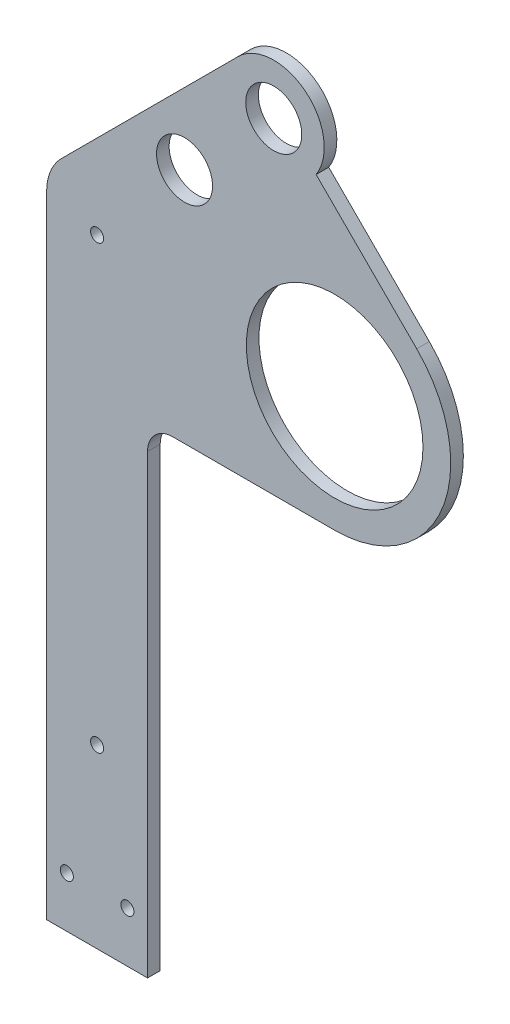
SolidWorks part; units mm, degrees
material "6061 合金"
ref_plane "前视基准面" through (0, 0, 0) normal (0, 0, 1) x (1, 0, 0)
ref_plane "上视基准面" through (0, 0, 0) normal (0, 1, 0) x (1, 0, 0)
ref_plane "右视基准面" through (0, 0, 0) normal (1, 0, 0) x (0, 0, -1)
other "Configuration Table"
sketch "草图1" plane through (0, 0, 0) normal (0, 0, 1) x (1, 0, 0)
  circle A0 centre (0, 0) radius 20
  circle A1 centre (0, 0) radius 11.1
  dimension "D1" = 40
  dimension "D2" = 22.2
extrude "凸台-拉伸1" add sketch "草图1" along normal blind 60 contours A1 | A0 region at (0, 0, 0)
ref_plane "基准面1" through (0, 0, 30) normal (0, 0, 1) x (1, 0, 0)
sketch "草图2" plane through (0, 0, 30) normal (0, 0, 1) x (1, 0, 0)
  line L0 (0, 0) -> (-70, -70) construction
  line L1 (-70, -70) -> (-70, -320) construction
  line L2 (0, -57.3148) -> (0, 49.9409) construction
  line L3 (-56.8582, 0) -> (46.4003, 0) construction
  line L4 (-14.1421, 14.1421) -> (-90, -61.7157)
  line L5 (14.1421, -14.1421) -> (-50, -78.2843)
  line L6 (-90, -61.7157) -> (-90, -320)
  line L7 (-50, -78.2843) -> (-50, -320)
  line L8 (-90, -320) -> (-50, -320)
  circle A2 centre (0, 0) radius 20 construction
  arc A3 (-14.1421, 14.1421) -> (14.1421, -14.1421) centre (0, 0) ccw
  dimension "D1" = 45
  dimension "D2" = 250
  dimension "D3" = 70
  dimension "D4" = 40
  dimension "D5" = 40
extrude "凸台-拉伸2" add sketch "草图2" along normal mid plane 60 contours L7 L8 L6 L4 A3 L5
sketch "草图4" plane through (0, 0, 60) normal (0, 0, 1) x (1, 0, 0)
  line L0 (-90, -61.7157) -> (-90, -320) construction
  line L1 (-90, -290) -> (-50, -290)
  line L2 (-90, -290) -> (-90, -350)
  line L4 (-50, -290) -> (-50, -350)
  line L5 (-50, -78.2843) -> (-50, -320) construction
  line L6 (-90, -320) -> (-50, -320) construction
  arc A0 (-90, -350) -> (-50, -350) centre (-70, -350) ccw
  circle A1 centre (-70, -350) radius 11
  dimension "D3" = 22
  dimension "D1" = 30
  dimension "D2" = 30
extrude "凸台-拉伸3" add sketch "草图4" along normal blind 5
mirror "镜向1" about plane through (0, 0, 30) normal (0, 0, 1) of "凸台-拉伸3"
sketch "草图5" plane through (0, 0, 0) normal (0, 1, 0) x (1, 0, 0)
  line L0 (0, 0) -> (0, -78.0582) construction
ref_plane "基准面2" through (-70, 0, 0) normal (-1, 0, 0) x (0, 0, 1)
sketch "草图7" plane through (-70, 0, 0) normal (-1, 0, 0) x (0, 0, 1)
  line L0 (-34.1239, -350) -> (109.535, -350) construction
sketch "草图8" plane through (0, 0, 60) normal (0, 0, 1) x (1, 0, 0)
  line L0 (0, 0) -> (-70, -70) construction
  circle A0 centre (-35.3553, -35.3553) radius 11.1
  dimension "D1" = 22.2
  dimension "D2" = 50
extrude "切除-拉伸1" cut sketch "草图8" against normal blind 100
fillet "圆角4" radius 20 2 edges at (-90, -61.7157, 30) (-50, -78.2843, 30)
fillet "圆角1" [suppressed] radius 50
fillet "圆角2" [suppressed] radius 3
sketch "草图9" plane through (0, 0, 65) normal (0, 0, 1) x (1, 0, 0)
  circle A0 centre (-70, -350) radius 13
  dimension "D1" = 26
extrude "切除-拉伸2" [suppressed] cut sketch "草图9" against normal blind 0.75
sketch "草图10" plane through (0, 0, -5) normal (0, 0, -1) x (-1, 0, 0)
  circle A0 centre (70, -350) radius 13
  dimension "D1" = 26
extrude "切除-拉伸3" [suppressed] cut sketch "草图10" against normal blind 0.75 contours A0
sketch "草图11" plane through (-90, 0, 0) normal (-1, 0, 0) x (0, 0, 1)
  circle A0 centre (48.5, -118.9949) radius 2.75
  circle A1 centre (48.5, -183.9949) radius 2.75
  circle A2 centre (48.5, -248.9949) radius 2.75
  circle A3 centre (11.5, -248.9949) radius 2.75
  circle A4 centre (11.5, -183.9949) radius 2.75
  circle A5 centre (11.5, -118.9949) radius 2.75
  dimension "D1" = 5.5
extrude "切除-拉伸4" [suppressed] cut sketch "草图11" against normal through all contours A1 | A2 | A0 | A3 | A4 | A5
sketch "草图12" [suppressed] plane through (-90, 0, 0) normal (-1, 0, 0) x (0, 0, 1)
  line L0 (30, -62.0134) -> (30, -339.6946) construction
  line L1 (10, -128.9949) -> (50, -128.9949)
  line L2 (10, -128.9949) -> (10, -173.9949)
  line L3 (10, -173.9949) -> (50, -173.9949)
  line L4 (50, -128.9949) -> (50, -173.9949)
  line L5 (10, -193.9949) -> (50, -193.9949)
  line L6 (10, -193.9949) -> (10, -238.9949)
  line L7 (10, -238.9949) -> (50, -238.9949)
  line L8 (50, -193.9949) -> (50, -238.9949)
  line L9 (10, -258.9949) -> (50, -258.9949)
  line L10 (10, -258.9949) -> (10, -290)
  line L11 (10, -290) -> (50, -290)
  line L12 (50, -258.9949) -> (50, -290)
  line L13 (19.5, -173.9949) -> (40.5, -173.9949)
  line L14 (19.5, -173.9949) -> (19.5, -193.9949)
  line L15 (19.5, -193.9949) -> (40.5, -193.9949)
  line L16 (40.5, -173.9949) -> (40.5, -193.9949)
  line L17 (19.5, -238.9949) -> (40.5, -238.9949)
  line L18 (19.5, -238.9949) -> (19.5, -258.9949)
  line L19 (19.5, -258.9949) -> (40.5, -258.9949)
  line L20 (40.5, -238.9949) -> (40.5, -258.9949)
  line L21 (60, -82.4264) -> (60, -290) construction
  line L22 (0, -290) -> (0, -82.4264) construction
  line L23 (57, -320) -> (3, -320) construction
  circle A0 centre (48.5, -118.9949) radius 2.75 construction
  circle A1 centre (48.5, -183.9949) radius 2.75 construction
  circle A2 centre (48.5, -248.9949) radius 2.75 construction
  dimension "D1" = 10
  dimension "D2" = 10
  dimension "D3" = 10
  dimension "D4" = 8
  dimension "D5" = 10
  dimension "D6" = 10
  dimension "D7" = 10
  dimension "D8" = 30
extrude "减重" [suppressed] cut sketch "草图12" against normal through all contours L0 L1 L2 L3 | L15 L0 L17 L7 L8 L5 | L0 L5 L6 L7 | L19 L0 L11 L12 L9 | L0 L9 L10 L11 | L1 L0 L13 L3 L4
fillet "圆角3" [suppressed] radius 3
sketch "草图13" plane through (0, 0, 60) normal (0, 0, 1) x (1, 0, 0)
  circle A0 centre (0, 0) radius 13
  circle A1 centre (-35.3553, -35.3553) radius 13
  dimension "D1" = 26
  dimension "D2" = 26
extrude "切除-拉伸6" [suppressed] cut sketch "草图13" against normal blind 1.75
sketch "草图14" plane through (0, 0, 0) normal (0, 0, -1) x (-1, 0, 0)
  circle A0 centre (0, 0) radius 13
  circle A1 centre (35.3553, -35.3553) radius 13
  dimension "D1" = 26
  dimension "D2" = 26
extrude "切除-拉伸7" [suppressed] cut sketch "草图14" against normal blind 1.75
sketch "草图15" [suppressed] plane through (0, 0, 0) normal (0, 0, -1) x (-1, 0, 0)
  line L0 (0, 0) -> (70, -350) construction
  line L1 (56.2719, -67.2005) -> (60.1942, -86.8121) construction
  line L2 (70, -350) -> (204.3541, -323.1292) construction
  circle A0 centre (56.2719, -67.2005) radius 2.75
  circle A1 centre (75.2172, -73.6095) radius 2.75
  circle A2 centre (60.1942, -86.8121) radius 2.75
  dimension "D1" = 5.5
  dimension "D2" = 20
  dimension "D3" = 20
  dimension "D4" = 20
  dimension "D5" = 42
  dimension "D6" = 270
extrude "切除-拉伸8" [suppressed] cut sketch "草图15" against normal through all contours A2 | A0 | A1
ref_plane "小腿主干连杆面" through (0, 0, 0) normal (0.9806, -0.1961, 0) x (0, 0, -1)
ref_plane "小腿主干对称面" through (0, 0, 30) normal (0, 0, -1) x (-1, 0, 0)
sketch "草图16" plane through (0, 0, 60) normal (0, 0, 1) x (1, 0, 0)
  line L0 (0, 0) -> (-70, -350)
  line L1 (-35.3553, -35.3553) -> (0, 0)
sketch "草图17" plane through (0, 0, 60) normal (0, 0, 1) x (1, 0, 0)
  line L0 (0, 0) -> (-70, -350) construction
  line L1 (118.6974, 32.5948) -> (32.9122, -396.3312) construction
  line L2 (92.7764, -97.0102) -> (24.1357, -83.2821)
  line L3 (73.1648, -195.0683) -> (4.5241, -181.3401)
  circle A0 centre (24.1357, -83.2821) radius 46
  circle A1 centre (4.5241, -181.3401) radius 46
  dimension "D3" = 92
  dimension "D4" = 92
  dimension "D1" = 110
  dimension "D2" = 70
  dimension "D5" = 180
  dimension "D6" = 280
sketch "草图18" plane through (0, 0, 60) normal (0, 0, 1) x (1, 0, 0)
  line L1 (14.1421, -14.1421) -> (-44.1421, -72.4264) construction
  line L3 (14.1421, -14.1421) -> (-44.1421, -72.4264)
  line L4 (16.784, -10.8765) -> (56.6627, -50.7551)
  line L5 (-50, -129.2821) -> (24.1357, -129.2821)
  line L10 (-90, -290) -> (-50, -290)
  line L11 (-50, -290) -> (-50, -86.5685)
  line L12 (-44.1421, -72.4264) -> (14.1421, -14.1421)
  line L13 (-14.1421, 14.1421) -> (-84.1421, -55.8579)
  line L14 (-90, -70) -> (-90, -290)
  line L16 (-50, -129.2821) -> (-50, -86.5685)
  line L17 (-44.1421, -72.4264) -> (14.1421, -14.1421)
  circle A0 centre (24.1357, -83.2821) radius 46 construction
  arc A1 (14.1421, -14.1421) -> (-14.1421, 14.1421) centre (0, 0) ccw construction
  arc A2 (14.1421, -14.1421) -> (-14.1421, 14.1421) centre (0, 0) ccw
  arc A3 (14.1421, -14.1421) -> (16.784, -10.8765) centre (0, 0) ccw
  arc A4 (24.1357, -129.2821) -> (56.6627, -50.7551) centre (24.1357, -83.2821) ccw
  circle A5 centre (24.1357, -83.2821) radius 35
  arc A9 (-84.1421, -55.8579) -> (-90, -70) centre (-70, -70) ccw
  arc A10 (-84.1421, -55.8579) -> (-90, -70) centre (-70, -70) ccw
  arc A11 (-44.1421, -72.4264) -> (-50, -86.5685) centre (-30, -86.5685) ccw
  arc A12 (-44.1421, -72.4264) -> (-50, -86.5685) centre (-30, -86.5685) ccw
  line M14 (-50, -290) -> (-50, -86.5685)
  line M15 (-44.1421, -72.4264) -> (14.1421, -14.1421)
  arc M16 (14.1421, -14.1421) -> (-14.1421, 14.1421) centre (0, 0) ccw
  arc M22 (-50, -86.5685) -> (-44.1421, -72.4264) centre (-30, -86.5685) cw
  dimension "D2" = 70
  dimension "D1" = 0
extrude "凸台-拉伸4" add sketch "草图18" against normal blind 5 from offset 25 contours L5 A4 L4 A5 M16 M15 M22 M14 region at (16.8604, -13.6397, 60) offset against normal yes
sketch "草图19" plane through (0, 0, 0) normal (0, 0, -1) x (-1, 0, 0)
  line L0 (50, -86.5685) -> (50, -290) construction
  line L1 (50, -135.3401) -> (50, -227.3401)
  line L2 (-4.5241, -135.3401) -> (50, -135.3401)
  line L3 (-4.5241, -227.3401) -> (50, -227.3401)
  circle A0 centre (-4.5241, -181.3401) radius 46 construction
  arc A1 (-4.5241, -135.3401) -> (-4.5241, -227.3401) centre (-4.5241, -181.3401) ccw
  circle A2 centre (-4.5241, -181.3401) radius 35
  dimension "D1" = 70
extrude "凸台-拉伸5" add sketch "草图19" against normal blind 5 from offset 25 offset against normal yes
fillet "圆角5" radius 10 2 edges at (-50, -227.3401, 27.5) (-50, -129.2821, 32.5)
sketch "草图21" plane through (0, 0, 65) normal (0, 0, 1) x (1, 0, 0)
  line L0 (-70, -350) -> (-70, -6.9331) construction
  circle A0 centre (-70, -75) radius 2.6
  circle A1 centre (-70, -250) radius 2.6
  circle A2 centre (-58, -300) radius 2.6
  circle A3 centre (-82, -300) radius 2.6
  dimension "D1" = 5.2
  dimension "D2" = 12
  dimension "D3" = 50
  dimension "D4" = 100
  dimension "D5" = 175
extrude "切除-拉伸9" cut sketch "草图21" against normal through all both and the other way through all
sketch "草图22" plane through (-90, 0, 0) normal (-1, 0, 0) x (0, 0, 1)
  line L0 (-5, -350) -> (-5, -370) construction
  line L5 (-5, -388.4633) -> (30, -388.4633)
  line L6 (-5, -388.4633) -> (-5, 64.9179)
  line L7 (-5, 64.9179) -> (30, 64.9179)
  line L8 (30, -388.4633) -> (30, 64.9179)
  line L10 (65, -370) -> (35, -370)
  line L11 (65, -370) -> (65, 61.088)
  line L12 (65, 61.088) -> (35, 61.088)
  line L13 (35, -370) -> (35, 61.088)
  dimension "D1" = 30
  dimension "D2" = 5
extrude "切除-拉伸10" cut sketch "草图22" against normal through all both contours L8 L7 L6 L5 | L13 L12 L11 L10
